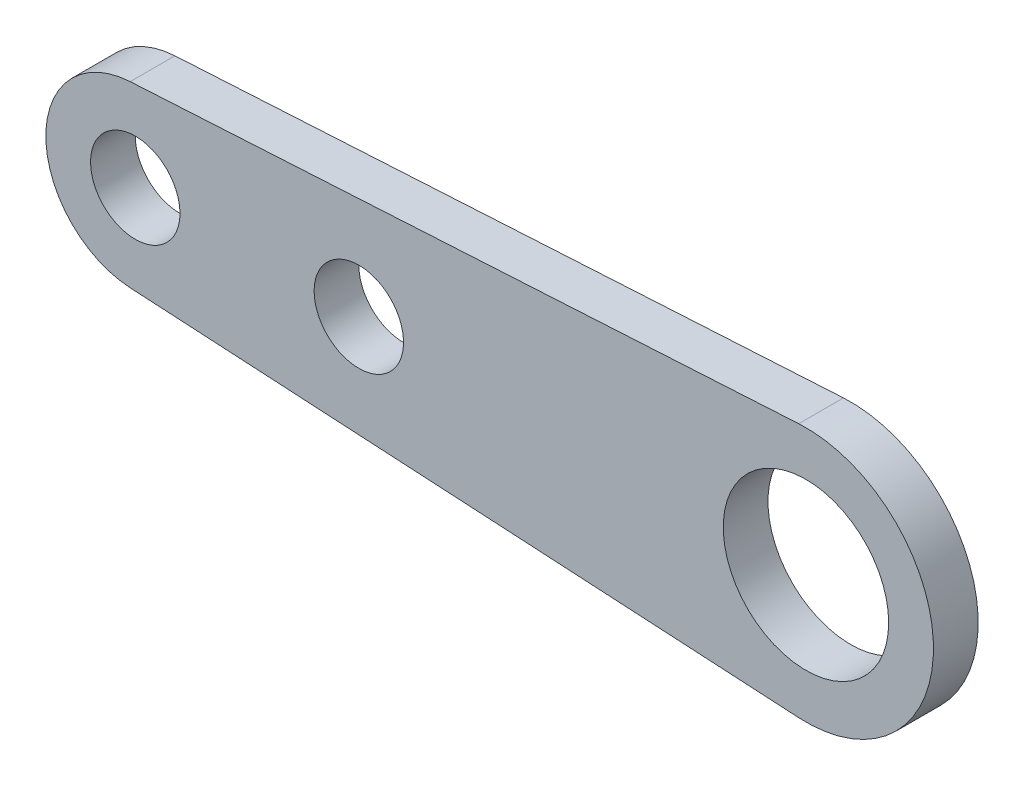
SolidWorks part; units mm, degrees
ref_plane "Front Plane" through (0, 0, 0) normal (1, 0, 0) x (0, 1, 0)
ref_plane "Top Plane" through (0, 0, 0) normal (0, 0, 1) x (0, 1, 0)
ref_plane "Right Plane" through (0, 0, 0) normal (0, 1, 0) x (-1, 0, 0)
sketch "Sketch1" plane through (0, 0, 0) normal (0, 0, 1) x (-1, 0, 0)
  line L0 (0, 0) -> (10.015, 0)
  line L16 (179.6503, 19.9677) -> (30.1337, 28.469)
  line L17 (198.515, 0) -> (188.515, 0)
  line L18 (198.515, 0) -> (198.515, 10) construction
  line L19 (81.0465, 10) -> (22.0572, 10) construction
  line L21 (138.515, 0) -> (168.515, 0)
  line L24 (47.015, 0) -> (118.515, 0)
  arc A10 (47.015, 0) -> (10.015, 0) centre (28.515, 0) ccw
  arc A11 (118.515, 0) -> (138.515, 0) centre (128.515, 0) cw
  arc A12 (168.515, 0) -> (188.515, 0) centre (178.515, 0) cw
  arc A13 (198.515, 0) -> (179.6503, 19.9677) centre (178.515, 0) ccw
  arc A14 (30.1337, 28.469) -> (0, 0) centre (28.515, 0) ccw
  dimension "D4" = 10
  dimension "D5" = 10
  dimension "D7" = 10
  dimension "D9" = 10
  dimension "D11" = 10.015
  dimension "D2" = 37
  dimension "D3" = 100
  dimension "D6" = 50
extrude "Boss-Extrude1" add sketch "Sketch1" along normal blind 10 contours A14 L0 A10 L24 A11 L21 A12 L17 A13 L16
mirror "Mirror1" about plane through (-47.015, 0, 10) normal (0, -1, 0) of "Boss-Extrude1"
ref_plane "Plane1" through (-28.515, 0, 0) normal (1, 0, 0) x (0, 0, -1)
equation "\"BearingBore\"=4"
equation "\"D4@Sketch1\"=\"BearingDiameter\""
equation "\"D5@Sketch1\"=\"BearingDiameter\""
equation "\"MinShinWidth\"= 20"
equation "\"D9@Sketch1\"=\"MinShinWidth\"/2"
equation "\"D2@Sketch1\" = \"MotorDiameter\""
equation "\"ShinThickness\"=10"
equation "\"PivotDistance\"=50"
equation "\"ThighLength\"= 200"
equation "\"HipBore\"=27"
equation "\"ThighThickness\"=30"
equation "\"MaxBending\"=135"
equation "\"MaxStretchingAngle\"= 140"
equation "\"ThighJointDistance\"=157.485"
equation "\"MotorDiameter\"= 37"
equation "\"ShinLength\"=100"
equation "\"D3@Sketch1\"=\"ShinLength\""
equation "\"BearingDiameter\"= 10"
equation "\"D1@Boss-Extrude1\"=\"ShinThickness\""
equation "\"D6@Sketch1\"=\"PivotDistance\""
